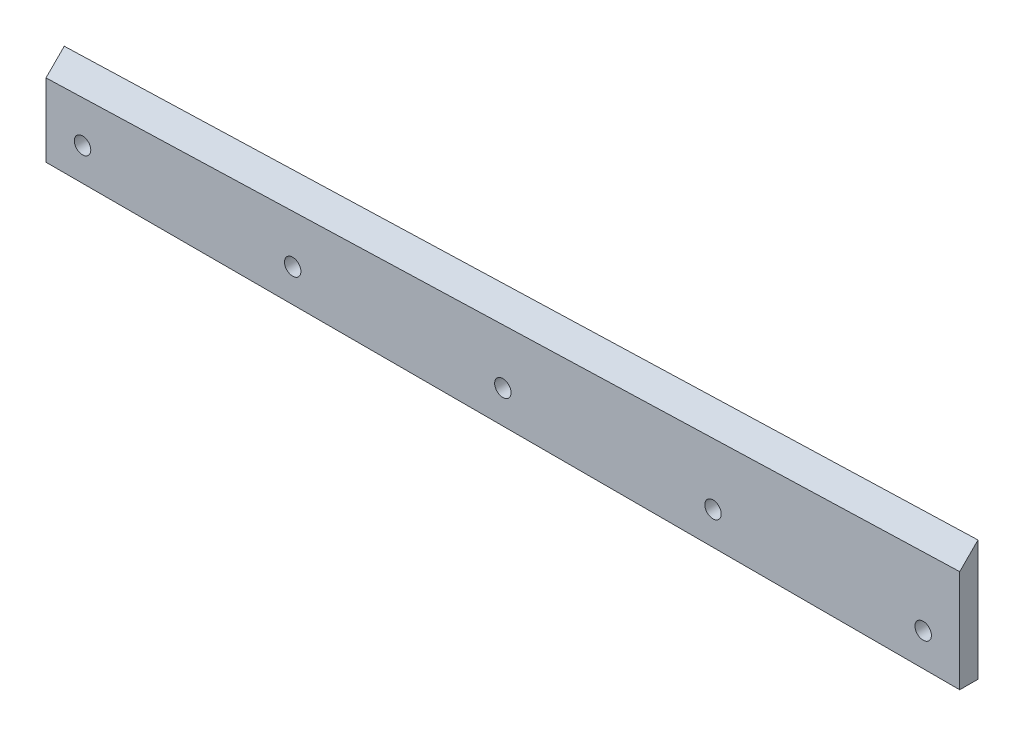
SolidWorks part; units mm, degrees
ref_plane "Front" through (0, 0, 0) normal (0, 0, 1) x (1, 0, 0)
ref_plane "Top" through (0, 0, 0) normal (0, 1, 0) x (1, 0, 0)
ref_plane "Right" through (0, 0, 0) normal (1, 0, 0) x (0, 0, -1)
sketch "Sketch1" plane through (0, 0, 0) normal (1, 0, 0) x (0, 0, -1)
  line L1 (0, 0) -> (-5, 0)
  line L2 (0, 0) -> (0, 33)
  line L3 (-5, 33) -> (0, 33)
  line L4 (-5, 0) -> (-5, 33)
  dimension "D1" = 5
  dimension "D2" = 33
extrude "Boss-Extrude1" add sketch "Sketch1" along normal blind 250
sketch "Sketch2" plane through (0, 0, 0) normal (0, 0, 1) x (1, 0, 0)
  line L0 (0, 33) -> (0, 25)
  line L1 (0, 25) -> (250, 33)
  line L2 (250, 33) -> (0, 33)
  line L3 (250, 33) -> (0, 33) construction
  line L4 (0, 33) -> (0, 0) construction
  line L5 (250, 33) -> (250, 0) construction
  dimension "D1" = 8
extrude "Cut-Extrude1" cut sketch "Sketch2" along normal through all
chamfer "Chamfer1" distance 5 angle 45 1 edges at (125, 29, 5)
hole_wizard "M4 Clearance Hole1" positions "Sketch3" profile "Sketch4" hole size "M4" standard "JIS" end condition through all
sketch "Sketch3" plane through (0, 0, 5) normal (0, 0, 1) x (1, 0, 0)
  line L0 (250, 27.9974) -> (250, 0) construction
  line L1 (250, 0) -> (0, 0) construction
  point P0 (240, 9)
  dimension "D1" = 10
  dimension "D2" = 9
sketch "Sketch4" plane through (240, 9, 5) normal (1, 0, 0) x (0, -1, 0)
  line L0 (0, 0) -> (0, 5)
  line L1 (0, 5) -> (2.25, 5)
  line L2 (2.25, 5) -> (2.25, 0)
  line L5 (2.25, 0) -> (0, 0)
  line L11 (0, -6.35) -> (0, 107.95) construction
  dimension "通し穴の直径" = 4.5
  dimension "通し穴の深さ" = 5
pattern_linear "LPattern1" count 5 spacing 57.5 along (-1, 0, 0) of "M4 Clearance Hole1"
